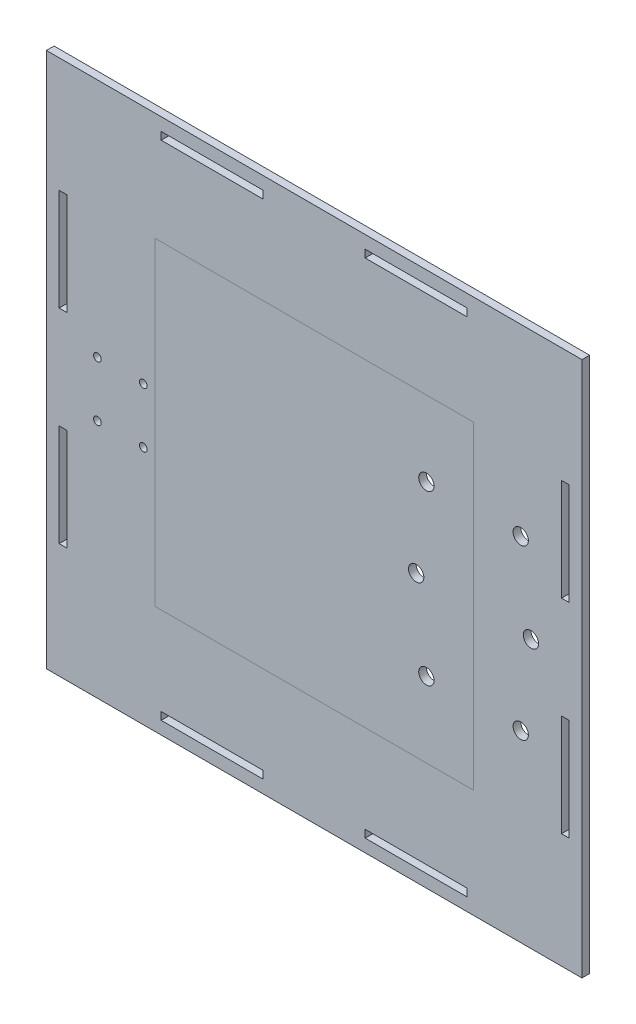
SolidWorks part; units mm, degrees
ref_plane "前视基准面" through (0, 0, 0) normal (0, 0, 1) x (1, 0, 0)
ref_plane "上视基准面" through (0, 0, 0) normal (0, 1, 0) x (1, 0, 0)
ref_plane "右视基准面" through (0, 0, 0) normal (1, 0, 0) x (0, 0, -1)
sketch "草图1" plane through (0, 0, 0) normal (0, 0, 1) x (1, 0, 0)
  line L0 (0, -100) -> (200, -100)
  line L1 (0, 0) -> (200, 0)
  line L2 (0, 0) -> (0, -200)
  line L3 (0, -200) -> (200, -200)
  line L4 (200, 0) -> (200, -200)
  line L5 (100, 0) -> (100, -200)
  line L6 (200, -80) -> (197, -80)
  line L7 (40, 0) -> (80, 0)
  line L8 (40, 0) -> (40, -3)
  line L9 (40, -3) -> (80, -3)
  line L10 (80, 0) -> (80, -3)
  line L11 (0, -40) -> (3, -40)
  line L12 (0, -40) -> (0, -80)
  line L13 (0, -80) -> (3, -80)
  line L14 (3, -40) -> (3, -80)
  line L15 (197, -40) -> (197, -80)
  line L16 (200, -40) -> (197, -40)
  line L17 (200, -40) -> (200, -80)
  line L18 (160, -3) -> (120, -3)
  line L19 (120, 0) -> (120, -3)
  line L20 (160, 0) -> (120, 0)
  line L21 (160, 0) -> (160, -3)
  line L22 (200, -160) -> (200, -120)
  line L23 (200, -160) -> (197, -160)
  line L24 (197, -160) -> (197, -120)
  line L25 (200, -120) -> (197, -120)
  line L26 (160, -200) -> (160, -197)
  line L27 (160, -200) -> (120, -200)
  line L28 (120, -200) -> (120, -197)
  line L29 (160, -197) -> (120, -197)
  line L30 (40, -197) -> (80, -197)
  line L31 (80, -200) -> (80, -197)
  line L32 (40, -200) -> (80, -200)
  line L33 (40, -200) -> (40, -197)
  line L34 (0, -120) -> (3, -120)
  line L35 (3, -160) -> (3, -120)
  line L36 (0, -160) -> (3, -160)
  line L37 (0, -160) -> (0, -120)
  line L38 (24, -86) -> (24, -114)
  line L39 (37.5, -37.5) -> (162.5, -37.5)
  line L40 (37.5, -37.5) -> (37.5, -162.5)
  line L41 (37.5, -162.5) -> (162.5, -162.5)
  line L42 (162.5, -37.5) -> (162.5, -162.5)
  line L43 (37.5, -37.5) -> (162.5, -162.5) construction
  line L44 (37.5, -162.5) -> (162.5, -37.5) construction
  line L45 (0, 0) -> (200, 0)
  line L46 (0, 0) -> (0, 5)
  line L47 (0, 5) -> (200, 5)
  line L48 (200, 0) -> (200, 5)
  line L49 (200, 5) -> (205, 5)
  line L50 (200, 5) -> (200, -200)
  line L51 (200, -200) -> (205, -200)
  line L52 (205, 5) -> (205, -200)
  line L53 (205, -200) -> (0, -200)
  line L54 (205, -200) -> (205, -205)
  line L55 (205, -205) -> (0, -205)
  line L56 (0, -200) -> (0, -205)
  line L57 (0, -205) -> (-5, -205)
  line L58 (0, -205) -> (0, 5)
  line L59 (0, 5) -> (-5, 5)
  line L60 (-5, -205) -> (-5, 5)
  line L61 (162.5, -57.5) -> (192.5, -57.5)
  line L62 (162.5, -57.5) -> (162.5, -142.5)
  line L63 (162.5, -142.5) -> (192.5, -142.5)
  line L64 (192.5, -57.5) -> (192.5, -142.5)
  line L65 (37.5, -86) -> (10.5, -86)
  line L66 (37.5, -86) -> (37.5, -114)
  line L67 (37.5, -114) -> (10.5, -114)
  line L68 (10.5, -86) -> (10.5, -114)
  circle A0 centre (185, -100) radius 3
  circle A1 centre (181, -67) radius 3
  circle A2 centre (181, -133) radius 3
  circle A3 centre (144, -133) radius 3
  circle A4 centre (140, -100) radius 3
  circle A5 centre (144, -67) radius 3
  circle A6 centre (33, -89.2) radius 1.5
  circle A7 centre (33, -110.8) radius 1.5
  circle A8 centre (15, -110.8) radius 1.5
  circle A9 centre (15, -89.2) radius 1.5
  point P41 (100, -100)
  dimension "D18" = 6
  dimension "D19" = 6
  dimension "D20" = 7.5
  dimension "D21" = 9.5
  dimension "D25" = 3
  dimension "D26" = 9
  dimension "D27" = 10.8
  dimension "D28" = 11.5
  dimension "D1" = 200
  dimension "D2" = 200
  dimension "D3" = 3
  dimension "D4" = 40
  dimension "D5" = 40
  dimension "D6" = 3
  dimension "D7" = 40
  dimension "D8" = 40
  dimension "D9" = 125
  dimension "D10" = 125
  dimension "D11" = 5
  dimension "D12" = 5
  dimension "D13" = 5
  dimension "D14" = 5
  dimension "D15" = 30
  dimension "D16" = 42.5
  dimension "D17" = 85
  dimension "D22" = 27
  dimension "D23" = 28
  dimension "D24" = 14
extrude "凸台-拉伸1" add sketch "草图1" along normal blind 3 contours L11 L14 L13 L2 L0 L5 L1 L10 L9 L8 | L36 L2 L3 L33 L30 L31 L5 L0 L34 L35 | L1 L21 L18 L19 L5 L0 L4 L6 L15 L16 | L29 L26 L3 L4 L23 L24 L25 L0 L5 L28 | L60 L57 L56 L2 L46 L59 | L1 L48 L47 L46 | L52 L49 L48 L4 L51 | L3 L56 L55 L54 L51 | A0 L0 L42 L63 L64 A2 | A0 L0 L64 L61 L42 A1 | L65 L68 L0 L38 A9 | L0 L68 L67 L38 A8 | L67 L40 L0 L38 A7 | L40 L65 L38 L0 A6 region at (39.2628, -34.4996, 0) region at (-2.5, -100, 0) region at (39.2628, -165.5004, 0) region at (17.3374, -93.1476, 0) region at (17.3374, -106.8524, 0) region at (30.6626, -93.1476, 0) region at (30.6626, -106.8524, 0) region at (100, 2.5, 0) region at (102.5, -202.5, 0) region at (157.3294, -27.0072, 0) region at (157.3294, -172.9928, 0) region at (202.5, -97.5, 0) region at (177.3337, -78.7904, 0) region at (177.3337, -121.2096, 0)
extrude "凸台-拉伸2" add sketch "草图1<3>" along normal blind 3 separate body contours L39 L40 L0 L5 | L40 L41 L5 L0 | L42 L0 L5 L41 | L42 L39 L5 L0 region at (68.75, -68.75, 0) region at (68.75, -131.25, 0) region at (131.1247, -68.6531, 0) region at (131.1247, -131.3469, 0)
sketch "草图1<3>" plane through (0, 0, 0) normal (0, 0, 1) x (1, 0, 0) same geometry as "草图1"
